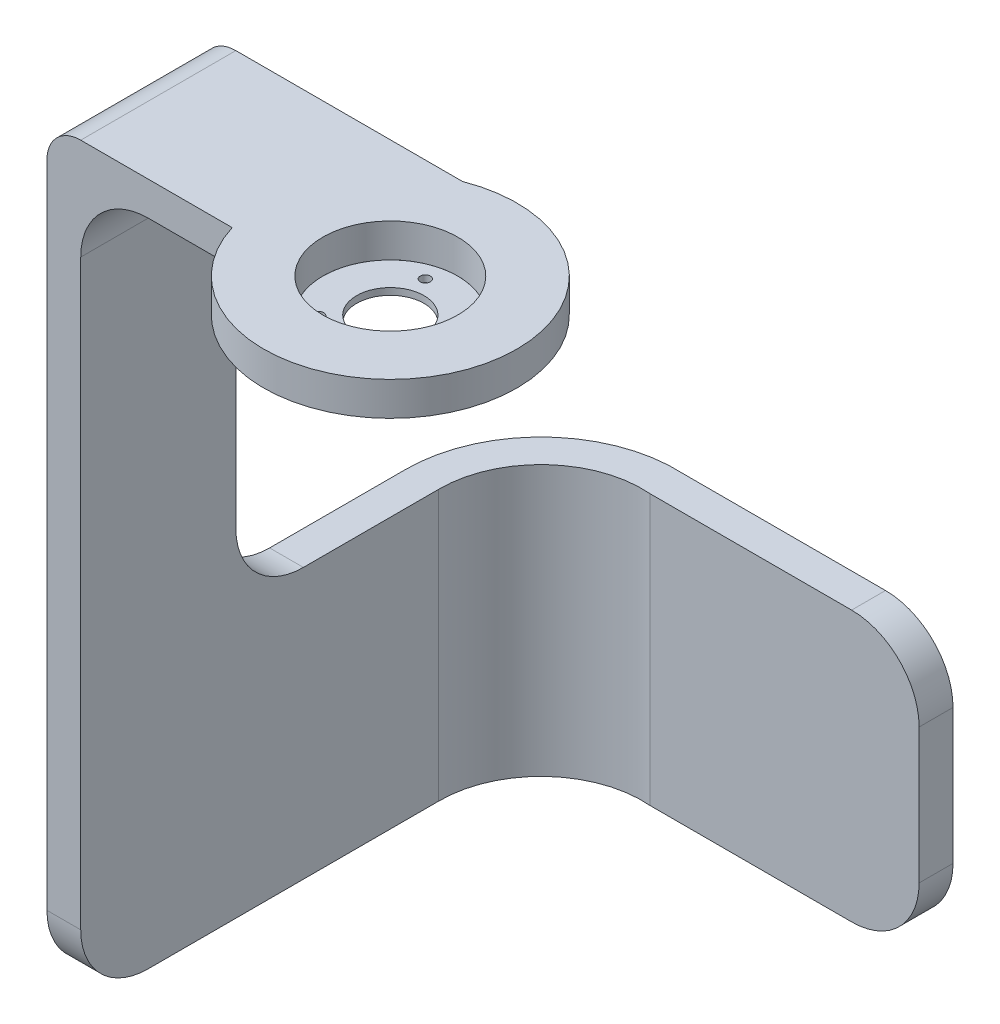
SolidWorks part; units mm, degrees
ref_plane "Plan de face" through (0, 0, 0) normal (0, 0, 1) x (1, 0, 0)
ref_plane "Plan de dessus" through (0, 0, 0) normal (0, 1, 0) x (1, 0, 0)
ref_plane "Plan de droite" through (0, 0, 0) normal (1, 0, 0) x (0, 0, -1)
sketch "Esquisse1" plane through (0, 0, 0) normal (0, 0, 1) x (1, 0, 0)
  line L0 (0, 72.643) -> (0, -62.4974) construction
  line L1 (61.973, 0) -> (-65.0509, 0) construction
sketch "Esquisse2" plane through (0, 0, 0) normal (0, 1, 0) x (1, 0, 0)
  line L0 (0, 20.8068) -> (0, -32.6644) construction
sketch "Esquisse3" plane through (0, 0, 0) normal (0, 1, 0) x (1, 0, 0)
  line L0 (-80.7194, 34.9627) -> (-13.5596, 34.9627)
  line L1 (-80.7194, 34.9627) -> (-80.7194, -10.9873)
  line L2 (-80.7194, -10.9873) -> (-35.8543, -10.9873)
  circle A0 centre (0, 0) radius 37.5
  dimension "D1" = 75
  dimension "D2" = 45.95
  dimension "D3" = 44.8652
  dimension "D4" = 67.1598
extrude "Boss.-Extru.1" add sketch "Esquisse3" along normal blind 10 contours A0 L1 | A0 region at (-56.1442, 0, -13.4721) region at (0, 0, 0)
sketch "Esquisse4" plane through (0, 10, 0) normal (0, 1, 0) x (1, 0, 0)
  circle A0 centre (0, 0) radius 20
  circle A1 centre (0, 0) radius 32.5
  dimension "D1" = 65
  dimension "D2" = 40
extrude "Enlèv. mat.-Extru.1" cut sketch "Esquisse4" against normal blind 10 contours A0
sketch "Esquisse7" plane through (-80.7194, 0, 0) normal (-1, 0, 0) x (0, 0, 1)
  line L0 (-34.9627, 10) -> (-34.9627, -212.5858)
  line L1 (-34.9627, -212.5858) -> (10.9873, -212.5858)
  line L2 (10.9873, -212.5858) -> (10.9873, 10)
  line L3 (10.9873, 10) -> (-34.9627, 10)
  line L5 (10.9873, 10) -> (10.9873, 0) construction
  dimension "D1" = 222.5858
extrude "Boss.-Extru.2" add sketch "Esquisse7" along normal blind 10
fillet "Congé1" radius 10 1 edges at (-90.7194, 10, -11.9877)
sketch "Esquisse8" plane through (0, -212.5858, 0) normal (0, -1, 0) x (1, 0, 0)
  line L0 (-80.7194, -34.9627) -> (-80.7194, -94.9627)
  line L3 (-90.72, -34.9627) -> (-80.7194, -34.9627)
  line L4 (-48.2681, -125.2207) -> (31.4253, -125.2207)
  line L5 (31.4253, -125.2207) -> (31.4253, -135.2635)
  line L6 (31.4253, -135.2635) -> (-48.5747, -135.2635)
  line L7 (-90.72, -94.9627) -> (-90.72, -34.9627)
  line L8 (-90.7194, -34.9627) -> (-80.7194, -34.9627) construction
  arc A2 (-80.7194, -94.9627) -> (-48.2681, -125.2207) centre (-50.7216, -95.3212) ccw
  arc A3 (-48.5747, -135.2635) -> (-90.72, -94.9627) centre (-50.7216, -95.3212) cw
  dimension "D1" = 30
  dimension "D2" = 40
  dimension "D5" = 60
  dimension "D3" = 80
  dimension "D4" = 60
  dimension "D6" = 122.1453
extrude "Boss.-Extru.3" add sketch "Esquisse8" against normal blind 80
fillet "Congé2" radius 20 5 edges at (-85.7194, -212.5858, 10.9873) (31.4253, -132.5858, -130.2421) (31.4253, -212.5858, -130.2421) (-85.7194, -132.5858, -34.9627) (-80.7194, 0, -11.9877)
sketch "Esquisse9" plane through (0, 0, -135.2635) normal (0, 0, -1) x (-1, 0, 0)
  line L0 (6.5747, -170.0878) -> (10.5747, -170.0878)
  line L3 (48.5747, -132.5858) -> (48.5747, -212.5858) construction
  line L4 (48.5747, -212.5858) -> (-11.4253, -212.5858) construction
  arc A2 (6.5747, -170.0878) -> (10.5747, -170.0878) centre (8.5747, -172.5858) ccw
  dimension "D1" = 4
  dimension "D2" = 3.2
  dimension "D3" = 40
  dimension "D4" = 40
extrude "Enlèv. mat.-Extru.2" cut sketch "Esquisse9" against normal blind 10
sketch "Esquisse13" plane through (0, 0, 10.9873) normal (0, 0, 1) x (1, 0, 0)
  line L0 (-90.7194, -20) -> (-100.7194, -20)
  line L1 (-90.7194, -192.5858) -> (-90.7194, 0) construction
  line L2 (-100.7194, -20) -> (-100.7194, -60)
  line L3 (-100.7194, -60) -> (-90.7194, -60)
  line L4 (-90.7194, -60) -> (-90.7194, -55)
  line L5 (-90.7194, -55) -> (-95.7194, -55)
  line L6 (-95.7194, -55) -> (-95.7194, -25)
  line L7 (-95.7194, -25) -> (-90.7194, -25)
  line L8 (-90.7194, -25) -> (-90.7194, -20)
  line L9 (61.973, 0) -> (-65.0509, 0) construction
  dimension "D1" = 40
  dimension "D2" = 30
  dimension "D3" = 5
  dimension "D4" = 10
  dimension "D5" = 20
  dimension "D6" = 5
extrude "Boss.-Extru.4" add sketch "Esquisse13" against normal blind 7 from offset 10 offset against normal yes
fillet "Congé3" radius 5 6 edges at (-95.7194, -25, -2.5127) (-95.7194, -55, -2.5127) (-90.7194, -60, -2.5127) (-90.7194, -20, -2.5127) (-100.7194, -60, -2.5127) (-100.7194, -20, -2.5127)
pattern_linear "Répétition linéaire1" count 2 spacing 20 along (0, 0, -1) of "Boss.-Extru.4"
fillet "Congé4" radius 5 6 edges at (-95.7194, -55, -22.5127) (-95.7194, -25, -22.5127) (-90.7194, -20, -22.5127) (-100.7194, -20, -22.5127) (-90.7194, -60, -22.5127) (-100.7194, -60, -22.5127)
sketch "Esquisse14" plane through (0, 0, 0) normal (0, -1, 0) x (1, 0, 0)
  circle A0 centre (0, 0) radius 20
extrude "Boss.-Extru.5" add sketch "Esquisse14" along normal blind 2 separate body
sketch "Esquisse17" plane through (0, -2, 0) normal (0, -1, 0) x (1, 0, 0)
  circle A0 centre (0, 0) radius 9.9784
  circle A1 centre (14.5403, 3.6852) radius 1.5
  circle A2 centre (-10.4616, 10.7496) radius 1.5
  circle A3 centre (-4.0787, -14.4348) radius 1.5
extrude "Enlèv. mat.-Extru.9" cut sketch "Esquisse17" against normal blind 2
